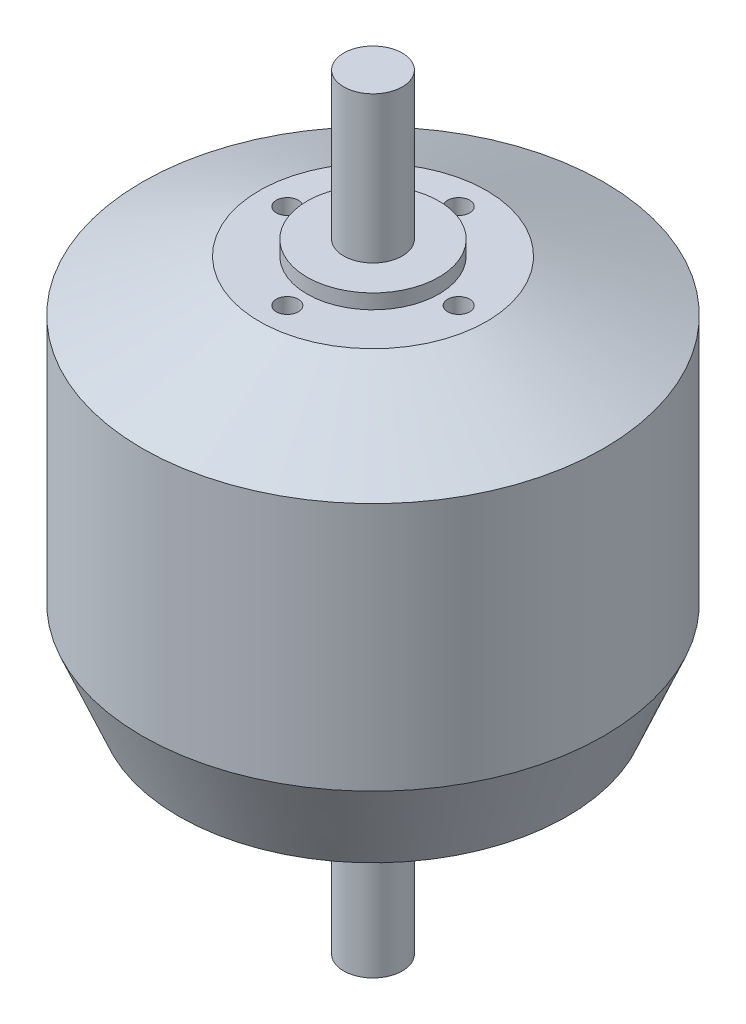
SolidWorks part; units mm, degrees
ref_plane "Front Plane" through (0, 0, 0) normal (0, 0, 1) x (1, 0, 0)
ref_plane "Top Plane" through (0, 0, 0) normal (0, 1, 0) x (1, 0, 0)
ref_plane "Right Plane" through (0, 0, 0) normal (1, 0, 0) x (0, 0, -1)
sketch "Sketch1" plane through (0, 0, 0) normal (0, 1, 0) x (1, 0, 0)
  line L0 (0, 0) -> (22.2, 0) construction
  circle A0 centre (0, 0) radius 4
  circle A1 centre (0, 0) radius 31.5
  circle A2 centre (0, 0) radius 9
  circle A3 centre (11.7, 0) radius 1.5
  circle A4 centre (22.2, 0) radius 2
  circle A5 centre (0, 11.7) radius 1.5
  circle A6 centre (0, 22.2) radius 2
  circle A7 centre (-11.7, 0) radius 1.5
  circle A8 centre (-22.2, 0) radius 2
  circle A9 centre (0, -11.7) radius 1.5
  circle A10 centre (0, -22.2) radius 2
  point P5 (11.7, 0)
  point P25 (0, 0)
  dimension "D1" = 8
  dimension "D2" = 63
  dimension "D3" = 18
  dimension "D6" = 3
  dimension "D7" = 4
  dimension "D4" = 22.2
  dimension "D5" = 11.7
  dimension "D8" = 4
extrude "Boss-Extrude1" add sketch "Sketch1" along normal blind 55 contours A1 A2 | A2 A0 | A0 | A10 | A9 | L0 A3 | A4 | A5 | A6 | A7 | A8 | A3 L0 region at (-8.7454, 0, 0) region at (22.2, 0, -1.9434) region at (11.7, 0, -0.6366) region at (11.7, 0, 0.6366) region at (-3.8869, 0, 0) region at (-30.609, 0, 0) region at (0, 0, -11.7) region at (0, 0, -22.2) region at (-11.7, 0, 0) region at (-22.2, 0, 0) region at (0, 0, 11.7) region at (0, 0, 22.2)
extrude "Cut-Extrude1" cut sketch "Sketch1<4>" against normal blind 2 from surface contours A1 A2 | A10 | A8 | A7 | A9 | A5 | L0 A3 | A4 | A3 L0 | A6 region at (22.2, 0, -1.9434) region at (11.7, 0, -0.6366) region at (11.7, 0, 0.6366) region at (-30.609, 0, 0) region at (0, 0, -11.7) region at (0, 0, -22.2) region at (-11.7, 0, 0) region at (-22.2, 0, 0) region at (0, 0, 11.7) region at (0, 0, 22.2) starting at face at (0, 55, 31.5)
sketch "Sketch1<4>" plane through (0, 0, 0) normal (0, 1, 0) x (1, 0, 0) same geometry as "Sketch1"
extrude "Boss-Extrude2" add sketch "Sketch1<5>" against normal blind 29.525 contours A0 region at (0, 0, 0)
sketch "Sketch1<5>" plane through (0, 0, 0) normal (0, 1, 0) x (1, 0, 0) same geometry as "Sketch1"
extrude "Cut-Extrude2" cut sketch "Sketch1<7>" along normal blind 10 contours A10 | A8 | A6 | A4 region at (22.2, 0, 0) region at (0, 0, -22.2) region at (-22.2, 0, 0) region at (0, 0, 22.2)
sketch "Sketch1<7>" plane through (0, 0, 0) normal (0, 1, 0) x (1, 0, 0) same geometry as "Sketch1"
extrude "Cut-Extrude3" cut sketch "Sketch1<10>" against normal blind 5 from surface contours A7 | A5 | L0 A3 | A3 L0 | A9 region at (11.7, 0, -0.6366) region at (11.7, 0, 0.6366) region at (0, 0, -11.7) region at (-11.7, 0, 0) region at (0, 0, 11.7) starting at face at (0, 53, 9)
sketch "Sketch1<10>" plane through (0, 0, 0) normal (0, 1, 0) x (1, 0, 0) same geometry as "Sketch1"
chamfer "Chamfer1" distance 5 distance2 12 1 edges at (0, 0, 31.5) first distance on face at (0, 0, 24.2)
chamfer "Chamfer2" distance 7 distance2 16 1 edges at (0, 53, 31.5) first distance on face at (0, 12, 31.5)
extrude "Boss-Extrude4" add sketch "Sketch1<11>" along normal blind 20 from surface contours A0 region at (0, 0, 0) starting at face at (0, 55, 9)
sketch "Sketch1<11>" plane through (0, 0, 0) normal (0, 1, 0) x (1, 0, 0) same geometry as "Sketch1"
